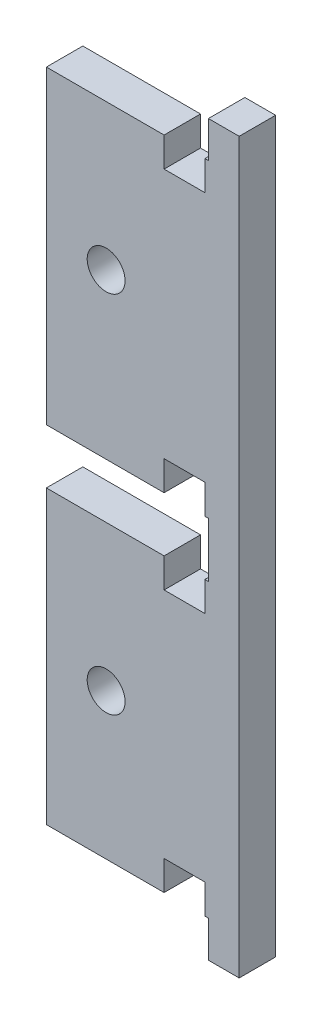
SolidWorks part; units mm, degrees
material "AISI 4130 Steel, annealed at 865C"
ref_plane "X-Y Datum" through (0, 0, 0) normal (0, 0, 1) x (1, 0, 0)
ref_plane "X-Z Datum" through (0, 0, 0) normal (0, 1, 0) x (1, 0, 0)
ref_plane "Y-Z Datum" through (0, 0, 0) normal (1, 0, 0) x (0, 0, -1)
sketch "Sketch2" plane through (0, 0, 0) normal (0, 0, 1) x (1, 0, 0)
  line L0 (32.9006, 127) -> (0, 127) construction
  line L1 (0, 0) -> (40.64, 0)
  line L2 (0, 0) -> (0, 127)
  line L3 (0, 127) -> (40.64, 127)
  line L4 (40.64, 0) -> (40.64, 127)
  point P7 (17.4625, 31.75)
  point P8 (17.4625, 95.25)
  dimension "D1" = 40.64
extrude "Boss-Extrude1" add sketch "Sketch2" along normal blind 6.35
hole_wizard "M6 Clearance Hole1" positions "Sketch3" profile "Sketch4" hole size "M6" standard "ANSI Metric" end condition through all
sketch "Sketch3" plane through (0, 0, 6.35) normal (0, 0, 1) x (1, 0, 0)
  point P0 (17.4625, 31.75)
  point P3 (17.4625, 95.25)
sketch "Sketch4" plane through (17.4625, 31.75, 6.35) normal (1, 0, 0) x (0, -1, 0)
  line L0 (0, 0) -> (0, 6.35)
  line L1 (0, 6.35) -> (3.3, 6.35)
  line L2 (3.3, 6.35) -> (3.3, 0)
  line L5 (3.3, 0) -> (0, 0)
  line L11 (0, -6.35) -> (0, 107.95) construction
  dimension "Thru Hole Dia." = 6.6
  dimension "Thru Hole Depth" = 6.35
sketch "Sketch5" plane through (0, 0, 6.35) normal (0, 0, 1) x (1, 0, 0)
  line L0 (7.0505, 127) -> (7.0505, 0)
  line L1 (40.64, 127) -> (0, 127) construction
  line L2 (0, 0) -> (40.64, 0) construction
  circle A0 centre (17.4625, 95.25) radius 3.3 construction
  point P6 (14.1625, 95.25)
  line M4 (0, 127) -> (0, 0)
  line M5 (0, 0) -> (40.64, 0)
  line M7 (40.64, 127) -> (0, 127)
  dimension "D1" = 7.112
extrude "Cut-Extrude1" cut sketch "Sketch5" against normal through all and the other way through all contours L0 M7 M4 M5 region at (3.5253, 63.5, 6.35)
sketch "Sketch6" plane through (0, 0, 6.35) normal (0, 0, 1) x (1, 0, 0)
  line L0 (-3.175, 120.65) -> (36.0756, 120.65)
  line L1 (36.0756, 120.65) -> (36.0756, 130.175)
  line L2 (36.0756, 130.175) -> (-3.175, 130.175)
  line L3 (-3.175, 130.175) -> (-3.175, 120.65)
  line L4 (0, 123.825) -> (32.9006, 123.825)
  line L5 (32.9006, 123.825) -> (32.9006, 127)
  line L6 (32.9006, 127) -> (0, 127)
  line L7 (0, 127) -> (0, 123.825)
  line L8 (0, 123.825) -> (32.9006, 123.825)
  line L9 (32.9006, 123.825) -> (32.9006, 127)
  line L10 (32.9006, 127) -> (0, 127)
  line L11 (0, 127) -> (0, 123.825)
  line L16 (0, 60.325) -> (32.9006, 60.325)
  line L17 (32.9006, 60.325) -> (32.9006, 63.5)
  line L18 (32.9006, 63.5) -> (0, 63.5)
  line L19 (0, 63.5) -> (0, 60.325)
  line L24 (0, 0) -> (34.925, 0)
  line L25 (34.925, 0) -> (34.925, 3.175)
  line L26 (34.925, 3.175) -> (0, 3.175)
  line L27 (0, 3.175) -> (0, 0)
  line L28 (36.0756, 66.675) -> (-3.175, 66.675)
  line L29 (-3.175, 66.675) -> (-3.175, 57.15)
  line L30 (-3.175, 57.15) -> (36.0756, 57.15)
  line L31 (36.0756, 57.15) -> (36.0756, 66.675)
  line L32 (38.1, 6.35) -> (-3.175, 6.35)
  line L33 (-3.175, 6.35) -> (-3.175, -3.175)
  line L34 (-3.175, -3.175) -> (38.1, -3.175)
  line L35 (38.1, -3.175) -> (38.1, 6.35)
  line L36 (35.2819, 127) -> (35.2819, 0)
  line L37 (40.64, 127) -> (7.0505, 127) construction
  line L38 (7.0505, 0) -> (40.64, 0) construction
  line M19 (7.0505, 127) -> (7.0505, 0)
  line M20 (7.0505, 0) -> (40.64, 0)
  line M22 (40.64, 127) -> (7.0505, 127)
  dimension "D5" = 2.3813
  dimension "D1" = 0
  dimension "D4" = 3.175
extrude "Cut-Extrude2" cut sketch "Sketch6" against normal through all contours L36 L9 L8 L0 M22 M19 | L8 L9 M22 M19 | L36 L28 L18 L17 L16 L30 M19 | L17 L18 L16 M19 | L36 L32 L26 L25 M19 M20 | L25 L26 M19 M20 region at (22.1716, 122.4845, 6.35) region at (19.9756, 125.4125, 6.35) region at (21.1662, 66.3771, 6.35) region at (19.9756, 61.9125, 6.35) region at (21.3402, 4.7229, 6.35) region at (20.9878, 1.5875, 6.35)
sketch "Sketch7" plane through (0, 0, 6.35) normal (0, 0, 1) x (1, 0, 0)
  line L0 (34.671, 115.5065) -> (27.559, 115.5065)
  line L5 (27.559, 121.031) -> (27.559, 115.5065)
  line L18 (34.29, 120.65) -> (27.94, 120.65)
  line L19 (34.29, 120.65) -> (34.29, 115.8875)
  line L20 (34.29, 115.8875) -> (27.94, 115.8875)
  line L21 (27.94, 120.65) -> (27.94, 115.8875)
  line L22 (34.29, 71.4375) -> (27.94, 71.4375)
  line L23 (34.29, 71.4375) -> (34.29, 66.675)
  line L24 (34.29, 66.675) -> (27.94, 66.675)
  line L25 (27.94, 71.4375) -> (27.94, 66.675)
  line L26 (34.29, 57.15) -> (27.94, 57.15)
  line L27 (34.29, 57.15) -> (34.29, 52.3875)
  line L28 (34.29, 52.3875) -> (27.94, 52.3875)
  line L29 (27.94, 57.15) -> (27.94, 52.3875)
  line L30 (34.29, 11.1125) -> (27.94, 11.1125)
  line L31 (34.29, 11.1125) -> (34.29, 6.35)
  line L32 (34.29, 6.35) -> (27.94, 6.35)
  line L33 (27.94, 11.1125) -> (27.94, 6.35)
  line L34 (34.671, 121.031) -> (27.559, 121.031)
  line L35 (34.671, 121.031) -> (34.671, 115.5065)
  line L36 (34.671, 66.294) -> (27.559, 66.294)
  line L37 (27.559, 71.8185) -> (27.559, 66.294)
  line L38 (34.671, 71.8185) -> (27.559, 71.8185)
  line L39 (34.671, 71.8185) -> (34.671, 66.294)
  line L40 (34.671, 52.0065) -> (27.559, 52.0065)
  line L41 (27.559, 57.531) -> (27.559, 52.0065)
  line L42 (34.671, 57.531) -> (27.559, 57.531)
  line L43 (34.671, 57.531) -> (34.671, 52.0065)
  line L44 (34.671, 5.969) -> (27.559, 5.969)
  line L45 (27.559, 11.4935) -> (27.559, 5.969)
  line L46 (34.671, 11.4935) -> (27.559, 11.4935)
  line L47 (34.671, 11.4935) -> (34.671, 5.969)
  line M4 (35.2819, 120.65) -> (7.0505, 120.65)
  line M6 (7.0505, 66.675) -> (35.2819, 66.675)
  line M8 (35.2819, 57.15) -> (7.0505, 57.15)
  line M10 (7.0505, 6.35) -> (35.2819, 6.35)
  dimension "D1" = 0.381
extrude "Cut-Extrude3" cut sketch "Sketch7" against normal through all contours L30 L33 L31 M10 | L47 L46 L45 L33 L30 L31 M10 | L47 L45 L44 M10 | L29 L28 L27 M8 | L43 L27 L28 L29 L41 L40 M8 | L43 L42 L41 M8 | L39 L37 L36 M6 | L22 L25 L23 M6 | L39 L38 L37 L25 L22 L23 M6 | L21 L20 L19 M4 | L35 L19 L20 L21 L5 L0 M4 | L35 L34 L5 M4 region at (31.115, 115.5943, 6.35) region at (31.115, 120.8405, 6.35) region at (31.115, 118.2688, 6.35) region at (31.115, 69.0563, 6.35) region at (31.115, 71.5253, 6.35) region at (31.115, 66.4845, 6.35) region at (31.115, 54.7688, 6.35) region at (34.4805, 57.0622, 6.35) region at (31.115, 57.3405, 6.35) region at (31.115, 8.7312, 6.35) region at (31.115, 11.2003, 6.35) region at (31.115, 6.1595, 6.35)
